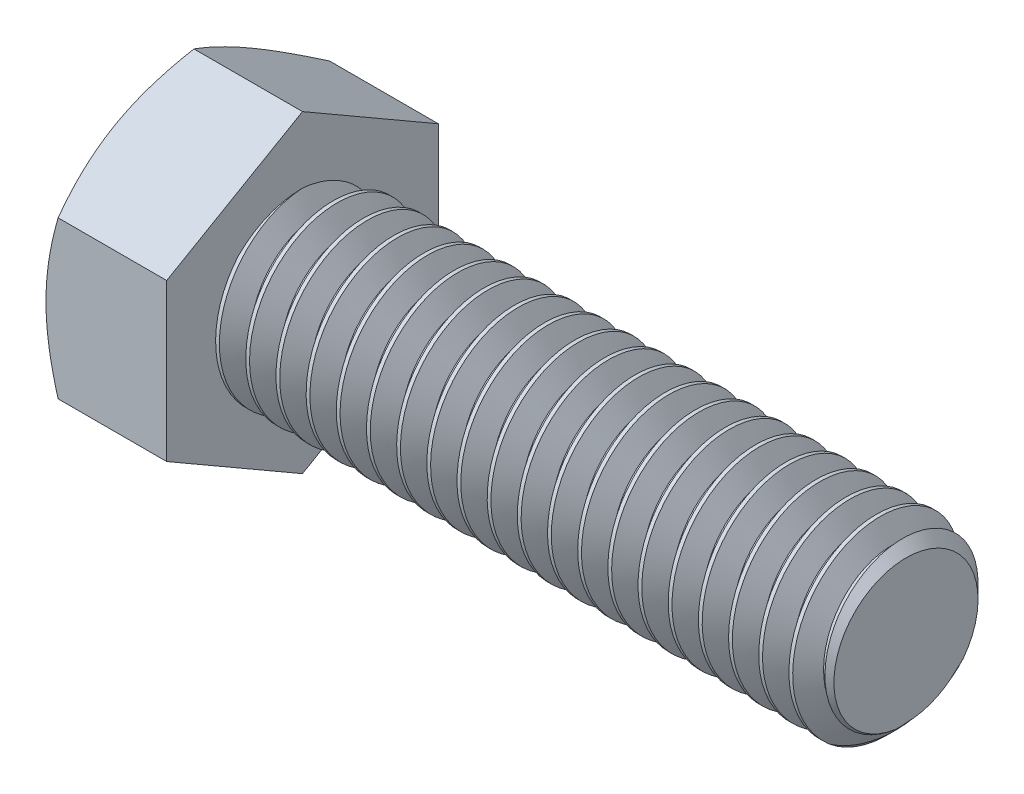
SolidWorks part; units mm, degrees
ref_plane "Front Plane" through (0, 0, 0) normal (0, 0, 1) x (1, 0, 0)
ref_plane "Top Plane" through (0, 0, 0) normal (0, 1, 0) x (1, 0, 0)
ref_plane "Right Plane" through (0, 0, 0) normal (1, 0, 0) x (0, 0, -1)
sketch "Sketch1" plane through (0, 0, 0) normal (0, 0, 1) x (1, 0, 0)
  line L0 (-19.05, 0) -> (19.05, 0) construction
  line L1 (19.05, 4.7625) -> (19.05, -4.7625) construction
  line L2 (-12.7, 7.1437) -> (-12.7, -7.1437) construction
  line L3 (-19.05, 7.1437) -> (-19.05, -7.1437) construction
  point P9 (-12.7, 0)
  point P10 (13.4938, -4.7625)
  dimension "D1" = 5.5562
  dimension "Screw Dia" = 9.525
  dimension "Hex" = 14.2875
  dimension "Head Ht" = 6.35
  dimension "Screw Lenght" = 31.75
ref_plane "Plane2" through (19.05, 0, 0) normal (1, 0, 0) x (0, 0, -1)
sketch "Sketch5" plane through (19.05, 0, 0) normal (1, 0, 0) x (0, 0, -1)
  circle A0 centre (0, 0) radius 4.7625
extrude "Boss-Extrude3" add sketch "Sketch5" against normal up to vertex (31.75 mm away) up to point (-12.7, 0, 0)
sketch "Sketch9" plane through (19.05, 0, 0) normal (1, 0, 0) x (0, 0, -1)
  circle A1 centre (0, 0) radius 4.7625
  circle A2 centre (0, 0) radius 4.7625
  dimension "D1" = 0
curve "Helix/Spiral1" pitch 1.5875 height 33.3375 turns 21 parameters "Pitch"=1.5875
chamfer "Chamfer1" distance 0.9715 angle 45 1 edges at (19.05, 0, -4.7625)
sketch "Sketch10" plane through (0, 0, 0) normal (0, 0, 1) x (1, 0, 0)
  line L0 (19.05, 4.7625) -> (19.6453, 3.7314)
  line L1 (19.6453, 3.7314) -> (19.8438, 3.7314)
  line L2 (19.8438, 3.7314) -> (20.4391, 4.7625)
  line L3 (19.05, 4.7625) -> (20.4391, 4.7625)
  line L4 (19.7445, 4.7625) -> (19.7445, 3.7314) construction
  line L5 (19.3477, 4.2469) -> (20.1414, 4.2469) construction
  dimension "D1" = 60
  dimension "D2" = 0.1984
  dimension "D3" = 0.7937
sweep "Cut-Sweep1" cut profiles "Sketch10" path "Helix/Spiral1"
sketch "Sketch6" plane through (-12.7, 0, 0) normal (-1, 0, 0) x (0, 0, 1)
  line L0 (0, 7.1437) -> (0, -7.1437) construction
  line L1 (7.1437, 4.1244) -> (0, 8.2489)
  line L2 (0, 8.2489) -> (-7.1438, 4.1244)
  line L3 (-7.1438, 4.1244) -> (-7.1438, -4.1244)
  line L4 (-7.1438, -4.1244) -> (0, -8.2489)
  line L5 (0, -8.2489) -> (7.1438, -4.1244)
  line L6 (7.1438, -4.1244) -> (7.1437, 4.1244)
  circle A0 centre (0, 0) radius 7.1438 construction
extrude "Boss-Extrude4" add sketch "Sketch6" along normal up to vertex (6.35 mm away) up to point (-19.05, -7.1437, 0)
sketch "Sketch7" plane through (-19.05, 0, 0) normal (-1, 0, 0) x (0, 0, 1)
  circle A0 centre (0, 0) radius 7.1438 construction
  circle A1 centre (0, 0) radius 7.1438
sketch "Sketch8" plane through (-19.05, 0, 0) normal (-1, 0, 0) x (0, 0, 1)
  circle A0 centre (0, 0) radius 7.1438 construction
  circle A1 centre (0, 0) radius 7.1438
extrude "Cut-Extrude3" cut sketch "Sketch8" against normal through all draft 60 flip side to cut
sketch "Sketch12" plane through (-19.05, 0, 0) normal (-1, 0, 0) x (0, 0, 1)
  line L0 (0, 5.5007) -> (0, 3.0718) construction
  line L1 (0.2143, 5.5007) -> (0.2143, 3.0718)
  line L2 (-0.2143, 5.5007) -> (-0.2143, 3.0718)
  line L3 (0, 4.7625) -> (0, -4.7625) construction
  arc A0 (0.2143, 5.5007) -> (-0.2143, 5.5007) centre (0, 5.5007) ccw
  arc A1 (-0.2143, 3.0718) -> (0.2143, 3.0718) centre (0, 3.0718) ccw
  circle A3 centre (0, 0) radius 2.8575 construction
  circle A4 centre (0, 0) radius 5.715 construction
  point P2 (0, 4.2862)
  dimension "D1" = 5.715
  dimension "D3" = 11.43
  dimension "D2" = 0.4286
extrude "Cut-Extrude4" cut sketch "Sketch12" against normal blind 0.254
pattern_circular "CirPattern1" count 3 over 360 about axis through (0, 0, 0) along (1, 0, 0) of "Cut-Extrude4"
equation "\"D2@Sketch10\" = \"Pitch@Helix/Spiral1\"*.125"
equation "\"D3@Sketch10\" = \"Pitch@Helix/Spiral1\"*.5"
equation "\"D1@Chamfer1\" = \"Pitch@Helix/Spiral1\"*.612"
equation "\"D1@Sketch12\" = \"Hex@Sketch1\"*.4"
equation "\"D3@Sketch12\" = \"Hex@Sketch1\"*.8"
equation "\"D2@Sketch12\" = \"Hex@Sketch1\"*.03"
equation "\"D1@Sketch1\" = \"Pitch@Helix/Spiral1\"*3.5"
equation "\"D3@Helix/Spiral1\" = \"Screw Lenght@Sketch1\"+\"Pitch@Helix/Spiral1\""
